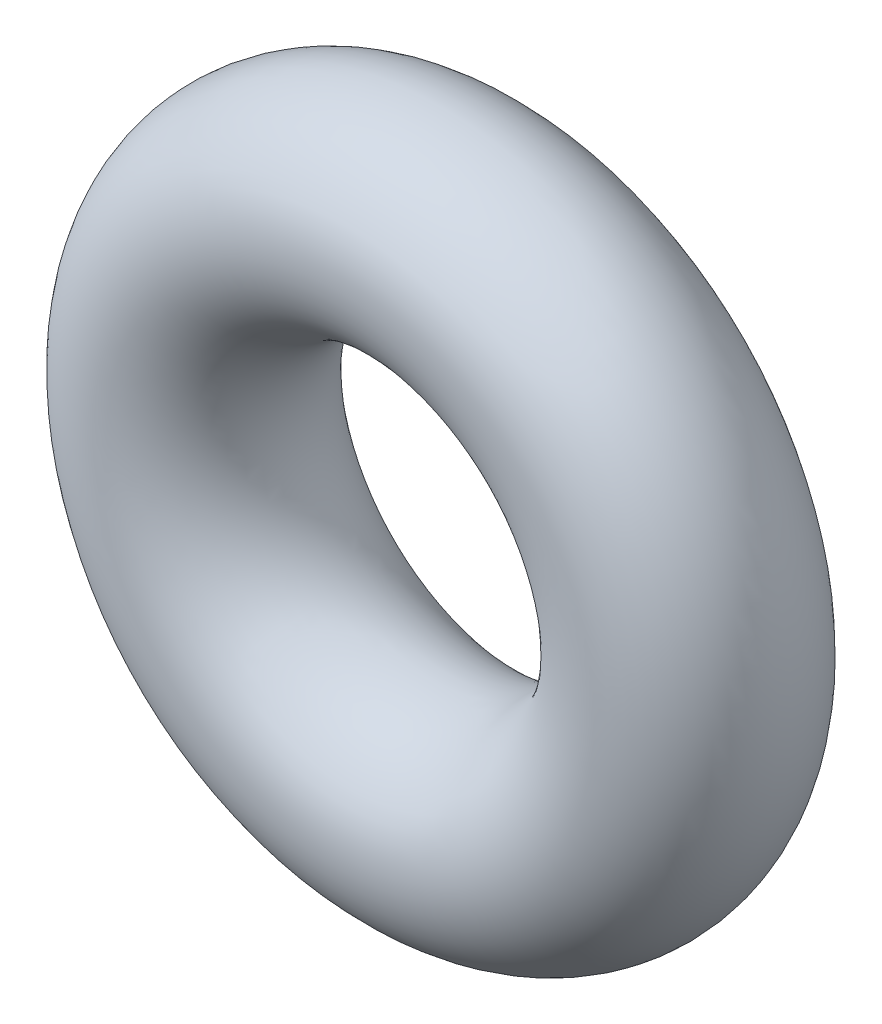
SolidWorks part; units mm, degrees
ref_plane "Front" through (0, 0, 0) normal (0, 0, 1) x (1, 0, 0)
ref_plane "Top" through (0, 0, 0) normal (0, 1, 0) x (1, 0, 0)
ref_plane "Right" through (0, 0, 0) normal (1, 0, 0) x (0, 0, -1)
sketch "Sketch1" plane through (0, 0, 0) normal (1, 0, 0) x (0, -1, 0)
  line L0 (0, -0.8) -> (0, 0.8) construction
  line L2 (-2.97, 0) -> (2.97, 0) construction
  line L3 (-1.1, 0) -> (1.1, 0) construction
  circle A0 centre (1.9, 0) radius 0.8
  point P9 (1.1, 0)
  point P10 (2.7, 0)
  point P13 (1.9, 0.8)
  point P14 (1.9, -0.8)
  dimension "Width" = 1.6
  dimension "ID" = 2.2
revolve "Revolve1" add sketch "Sketch1" angle 360 about L0
ref_axis "Axis1" through (0, 0, -0.88) along (0, 0, 1)
